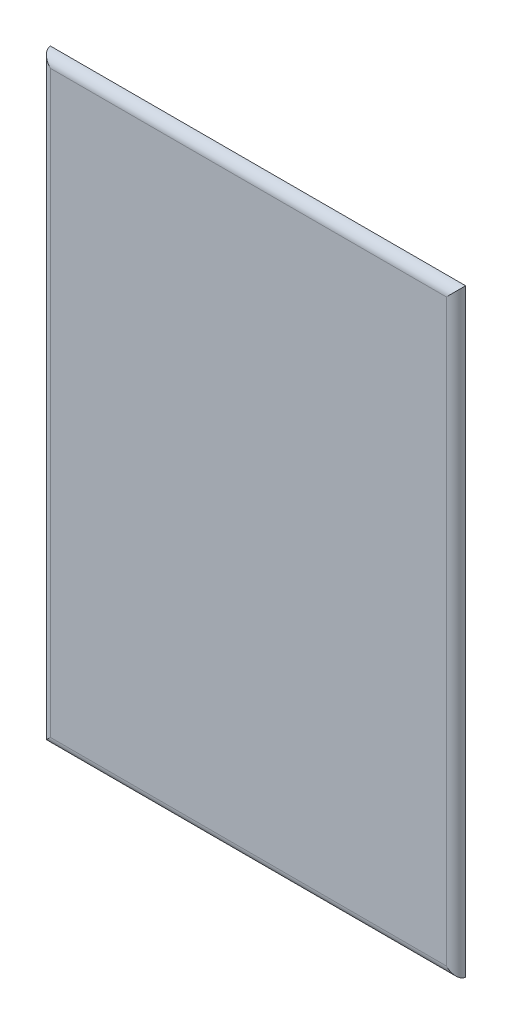
SolidWorks part; units mm, degrees
ref_plane "Front Plane" through (0, 0, 0) normal (0, 0, 1) x (1, 0, 0)
ref_plane "Top Plane" through (0, 0, 0) normal (0, 1, 0) x (1, 0, 0)
ref_plane "Right Plane" through (0, 0, 0) normal (1, 0, 0) x (0, 0, -1)
sketch "Sketch1" plane through (0, 0, 0) normal (0, 0, 1) x (1, 0, 0)
  line L1 (0, 0) -> (273.05, 0)
  line L2 (0, 0) -> (0, 393.7)
  line L3 (0, 393.7) -> (273.05, 393.7)
  line L4 (273.05, 0) -> (273.05, 393.7)
  dimension "D1" = 393.7
  dimension "D2" = 273.05
extrude "Boss-Extrude1" add sketch "Sketch1" along normal blind 6.35
fillet "Fillet1" radius 6.35 4 edges at (136.525, 393.7, 6.35) (273.05, 196.85, 6.35) (136.525, 0, 6.35) (0, 196.85, 6.35)
